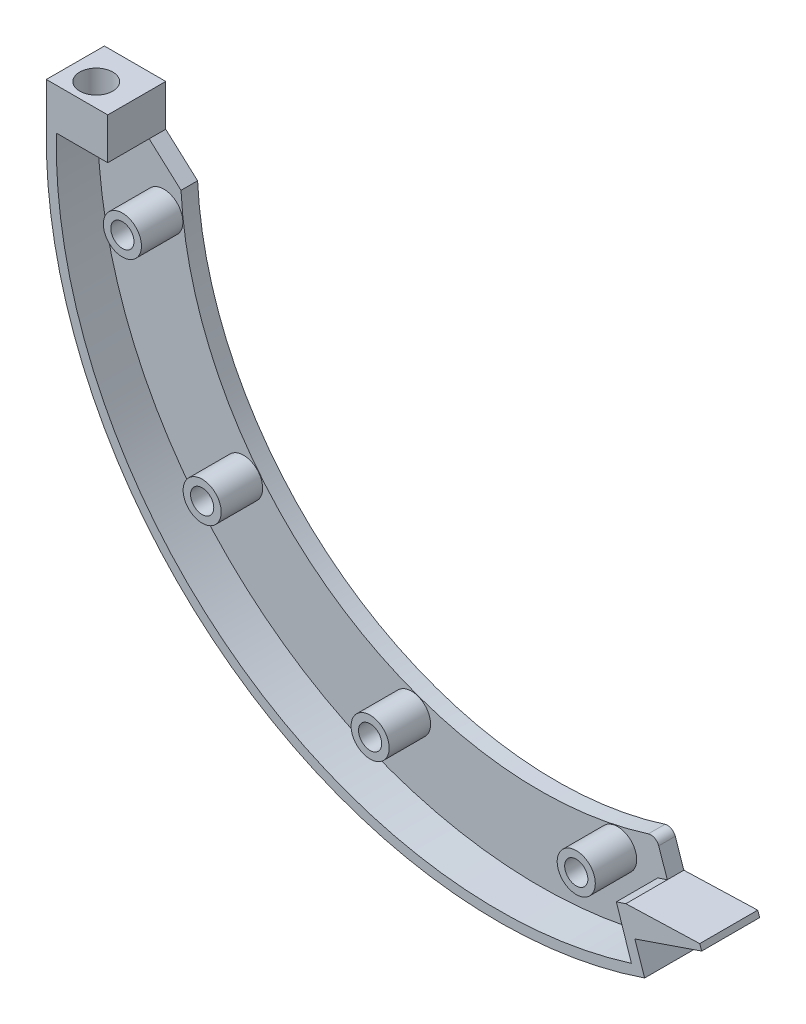
SolidWorks part; units mm, degrees
ref_plane "前视基准面" through (0, 0, 0) normal (0, 0, 1) x (1, 0, 0)
ref_plane "上视基准面" through (0, 0, 0) normal (0, 1, 0) x (1, 0, 0)
ref_plane "右视基准面" through (0, 0, 0) normal (1, 0, 0) x (0, 0, -1)
sketch "Sketch1" plane through (0, 0, 0) normal (0, 0, 1) x (1, 0, 0)
  line L2 (16.8879, -133.3693) -> (14.6737, -134.1273)
  line L3 (14.6737, -134.1273) -> (15.8677, -137.6154)
  line L5 (-48.9405, -84.8) -> (-45.0968, -88.2603)
  line L7 (-48.9405, -84.8) -> (-56.3425, -84.8)
  line L8 (12.5607, -127.9544) -> (13.5977, -130.9838)
  line L10 (16.8879, -133.3693) -> (22.7495, -131.3629)
  line L11 (22.5089, -130.6992) -> (22.7495, -131.3629)
  line L12 (13.5977, -130.9838) -> (22.5089, -130.6992)
  arc A0 (12.5607, -127.9544) -> (11.3122, -127.3251) centre (11.6146, -128.2783) ccw
  arc A6 (-56.3425, -84.8) -> (15.8677, -137.6154) centre (-1.8002, -86) ccw
  arc A9 (-45.0968, -88.2603) -> (11.3122, -127.3251) centre (-1.8002, -86) ccw
  dimension "D1" = 1
extrude "Boss-Extrude1" add sketch "Sketch1" along normal blind 2
sketch "Sketch2" plane through (0, 0, 2) normal (0, 0, 1) x (1, 0, 0)
  line L1 (-56.3425, -84.8) -> (-55.1422, -84.8)
  line L6 (22.5089, -130.6992) -> (13.5977, -130.9838)
  line L7 (-48.9405, -84.8) -> (-56.3425, -84.8)
  line L10 (14.2618, -136.8805) -> (12.45, -131.3605)
  line L11 (15.8677, -137.6154) -> (13.5977, -130.9838)
  line L12 (13.5977, -130.9838) -> (12.45, -131.3605)
  line L14 (-45.0968, -88.2603) -> (-48.9405, -84.8)
  line L18 (22.7495, -131.3629) -> (22.5089, -130.6992)
  line L23 (13.5977, -130.9838) -> (12.5607, -127.9544)
  line L25 (15.8677, -137.6154) -> (14.6737, -134.1273)
  line L27 (14.6737, -134.1273) -> (22.7495, -131.3629)
  arc A0 (-56.3557, -86) -> (-56.3425, -84.8) centre (-1.8002, -86) cw
  arc A1 (-55.1557, -86) -> (-55.1422, -84.8) centre (-1.8002, -86) cw
  arc A2 (15.2133, -137.8348) -> (15.8677, -137.6154) centre (-1.8002, -86) ccw
  arc A3 (12.5607, -127.9544) -> (11.3122, -127.3251) centre (11.6146, -128.2783) ccw
  arc A4 (-55.1557, -86) -> (14.2618, -136.8805) centre (-1.8002, -86) ccw
  arc A6 (-56.3425, -84.8) -> (15.8677, -137.6154) centre (-1.8002, -86) ccw
  arc A7 (-45.0968, -88.2603) -> (11.3122, -127.3251) centre (-1.8002, -86) ccw
  arc A8 (-56.3557, -86) -> (15.2133, -137.8348) centre (-1.8002, -86) ccw
  dimension "D1" = 0
extrude "Boss-Extrude2" add sketch "Sketch2" along normal blind 5
sketch "Sketch3" plane through (0, 0, 2) normal (0, 0, 1) x (1, 0, 0)
  line L0 (-1.8002, -86) -> (12.1201, -152.1768) construction
  line L1 (14.6737, -134.1273) -> (22.7495, -131.3629) construction
  line L4 (22.7495, -131.3629) -> (22.5089, -130.6992) construction
  line L5 (22.5089, -130.6992) -> (13.5977, -130.9838) construction
  line L6 (14.6737, -134.1273) -> (22.7495, -131.3629)
  line L7 (22.7495, -131.3629) -> (22.5089, -130.6992)
  line L8 (22.5089, -130.6992) -> (13.5977, -130.9838)
  line L9 (13.5977, -130.9838) -> (14.6737, -134.1273)
  circle A2 centre (7.6073, -130.7228) radius 2.3
  circle A3 centre (-17.2718, -129.003) radius 2.3
  circle A4 centre (-37.5439, -114.4784) radius 2.3
  circle A5 centre (-47.1727, -91.4738) radius 2.3
  point P13 (-1.8002, -86)
  dimension "D1" = 4.6
  dimension "D2" = 4
extrude "Boss-Extrude3" add sketch "Sketch3" along normal blind 5
sketch "Sketch4" plane through (0, -84.8, 0) normal (0, 1, 0) x (1, 0, 0)
  line L0 (-56.3425, -7) -> (-56.3425, 0) construction
  line L1 (-56.3425, 0) -> (-48.9405, 0)
  line L2 (-56.3425, 0) -> (-56.3557, -7)
  line L3 (-56.3557, -7) -> (-48.9405, -7)
  line L4 (-48.9405, 0) -> (-48.9405, -7)
  line L5 (-48.9405, 0) -> (-56.3425, 0) construction
  line L7 (-55.1557, -7) -> (-56.3557, -7) construction
extrude "Boss-Extrude4" add sketch "Sketch4" along normal blind 5
sketch "Sketch6" plane through (0, 0, 7) normal (0, 0, 1) x (1, 0, 0)
  circle A0 centre (-47.1727, -91.4738) radius 1.4
  circle A1 centre (-37.5439, -114.4784) radius 1.4
  circle A2 centre (-17.2718, -129.003) radius 1.4
  circle A3 centre (7.6073, -130.7228) radius 1.4
extrude "Cut-Extrude1" cut sketch "Sketch6" against normal blind 5
sketch "Sketch7" plane through (0, -79.8, 0) normal (0, 1, 0) x (1, 0, 0)
  circle A1 centre (-53.1133, -4.2128) radius 2
extrude "Cut-Extrude2" cut sketch "Sketch7" against normal blind 8
